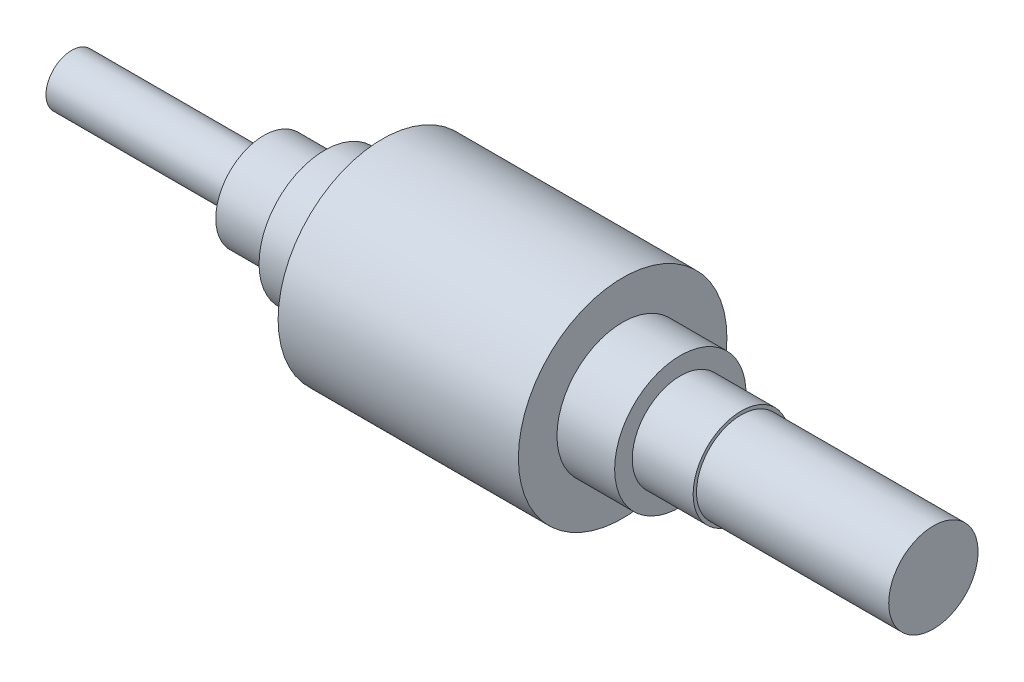
SolidWorks part; units mm, degrees
ref_plane "Ön Düzlem" through (0, 0, 0) normal (0, 0, 1) x (1, 0, 0)
ref_plane "Üst Düzlem" through (0, 0, 0) normal (0, 1, 0) x (1, 0, 0)
ref_plane "Sağ Düzlem" through (0, 0, 0) normal (1, 0, 0) x (0, 0, -1)
sketch "Çizim1" plane through (0, 0, 0) normal (0, 0, 1) x (1, 0, 0)
  line L1 (30, 7.5) -> (39.5, 7.5)
  line L2 (39.5, 7.5) -> (39.5, 10.25)
  line L3 (39.5, 10.25) -> (48.5, 10.25)
  line L4 (48.5, 10.25) -> (48.5, 16.275)
  line L5 (48.5, 16.275) -> (86, 16.275)
  line L6 (86, 16.275) -> (86, 10.25)
  line L7 (86, 10.25) -> (95, 10.25)
  line L8 (95, 10.25) -> (95, 7.5)
  line L10 (134.5, 6.975) -> (134.5, 0)
  line L11 (0, 0) -> (50000, 0) construction
  line L12 (0, 0) -> (134.5, 0)
  line L13 (95, 7.5) -> (104.5, 7.5)
  line L14 (104.5, 7.5) -> (104.5, 6.975)
  line L15 (104.5, 6.975) -> (134.5, 6.975)
  line L16 (30, 7.5) -> (30, 4)
  line L17 (30, 4) -> (0, 4)
  line L18 (0, 4) -> (0, 0)
  dimension "D2" = 7.5
  dimension "D3" = 9
  dimension "D4" = 10.25
  dimension "D5" = 37.5
  dimension "D6" = 6.975
  dimension "D7" = 7.5
  dimension "D8" = 16.275
  dimension "D9" = 9
  dimension "D10" = 9.5
  dimension "D11" = 10.25
  dimension "D12" = 30
  dimension "D13" = 9.5
  dimension "D14" = 30
  dimension "D15" = 4
revolve "Döndür1" add sketch "Çizim1" angle 360 about L11
